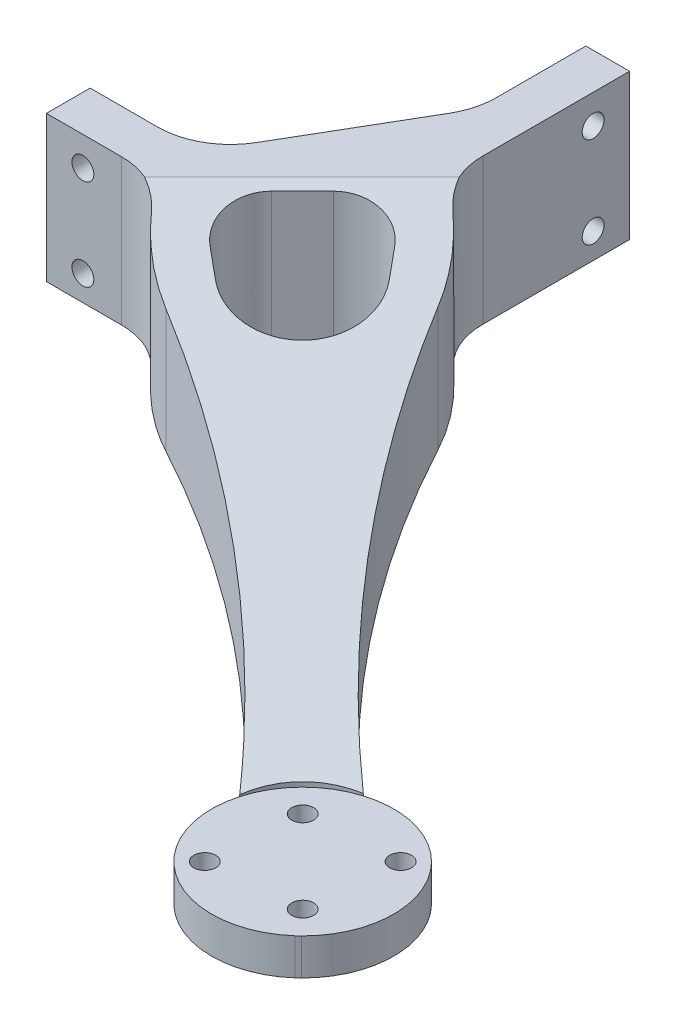
SolidWorks part; units mm, degrees
ref_plane "Front Plane" through (0, 0, 0) normal (0, 0, 1) x (1, 0, 0)
ref_plane "Top Plane" through (0, 0, 0) normal (0, 1, 0) x (1, 0, 0)
ref_plane "Right Plane" through (0, 0, 0) normal (1, 0, 0) x (0, 0, -1)
sketch "Sketch1" plane through (0, 0, 0) normal (0, 1, 0) x (1, 0, 0)
  line L0 (-32.8333, 3.1667) -> (-17.8333, 3.1667)
  line L1 (-17.8333, 3.1667) -> (7.1667, 18.1667)
  line L2 (7.1667, 18.1667) -> (7.1667, 33.1667)
  line L3 (7.1667, 33.1667) -> (12.1667, 33.1667)
  line L4 (12.1667, 33.1667) -> (12.1667, 18.1667)
  line L8 (-7.8333, -1.8333) -> (-32.8333, -1.8333)
  line L9 (-32.8333, -1.8333) -> (-32.8333, 3.1667)
  line L11 (12.1667, 18.1667) -> (17.5272, 18.1667)
  line L12 (-7.8333, -1.8333) -> (-7.8333, -7.1938)
  arc A0 (56.4946, -55.8323) -> (66.1657, -46.1613) centre (65.8063, -55.4729) ccw
  arc A1 (56.4946, -55.8323) -> (-7.8333, -7.1938) centre (-62.8059, -146.7575) ccw
  arc A2 (17.5272, 18.1667) -> (66.1657, -46.1613) centre (157.0908, 73.1392) ccw
  dimension "D1" = 15
  dimension "D2" = 5
  dimension "D3" = 15
  dimension "D4" = 5
  dimension "D5" = 25
  dimension "D6" = 25
  dimension "D7" = 15
  dimension "D8" = 15
  dimension "D11" = 155
  dimension "D14" = 155
extrude "Boss-Extrude3" add sketch "Sketch1" along normal blind 25
chamfer "Chamfer2" distance 6 angle 33 2 edges at (-7.8333, 12.5, 7.1938) (17.5272, 12.5, -18.1667) first distance on face at (-7.8333, 12.5, 4.5136) first distance on face at (39.6443, 12.5, 15.6623)
fillet "Fillet2" radius 30 2 edges at (19.7268, 12.5, -12.8805) (-2.8836, 12.5, 9.2464)
sketch "Sketch2" plane through (0, 0, 1.8333) normal (0, 0, 1) x (1, 0, 0)
  line L0 (-32.8333, 0) -> (-7.5027, 0) construction
  circle A0 centre (-27.8333, 20) radius 1.5
  circle A1 centre (-27.8333, 7.5) radius 1.5
  dimension "D1" = 20
  dimension "D3" = 12.5
  dimension "D2" = 35
extrude "Cut-Extrude1" cut sketch "Sketch2" against normal blind 25
sketch "Sketch3" plane through (12.1667, 0, 0) normal (1, 0, 0) x (0, 0, -1)
  line L0 (18.0687, 25) -> (33.1667, 25) construction
  circle A0 centre (28.1667, 20) radius 1.5
  circle A1 centre (28.1667, 7.5) radius 1.5
  dimension "D1" = 25
  dimension "D3" = 12.5
  dimension "D2" = 5
extrude "Cut-Extrude2" cut sketch "Sketch3" against normal blind 25
sketch "Sketch4" plane through (0, 25, 0) normal (0, 1, 0) x (1, 0, 0)
  line L0 (17.1652, 5.2091) -> (10.4484, 13.8698)
  line L1 (10.4484, 13.8698) -> (-3.4214, 0)
  line L2 (-3.4214, 0) -> (5.2393, -6.7168)
  arc A0 (56.4946, -55.8323) -> (4.4419, -12.6764) centre (-62.8059, -146.7575) ccw construction
  arc A1 (22.8804, 6.15) -> (66.1657, -46.1613) centre (157.0908, 73.1392) ccw construction
  arc A2 (22.8804, 6.15) -> (66.1657, -46.1613) centre (157.0908, 73.1392) ccw construction
  arc A4 (5.2393, -6.7168) -> (17.1652, 5.2091) centre (10.4484, 0) ccw
extrude "Cut-Extrude4" cut sketch "Sketch4" against normal blind 25
fillet "Fillet3" radius 6 2 edges at (10.4484, 12.5, -13.8698) (-3.4214, 12.5, 0)
sketch "Sketch7" plane through (0, 25, 0) normal (0, 1, 0) x (1, 0, 0)
  line L0 (8.9535, 27.4642) -> (42.7588, -6.3411)
  line L1 (42.7588, -6.3411) -> (46.7756, -2.3243)
  line L2 (46.7756, -2.3243) -> (12.9703, 31.481)
  line L3 (12.9703, 31.481) -> (8.9535, 27.4642)
extrude "Boss-Extrude4" add sketch "Sketch7" along normal blind 25
sketch "Sketch10" plane through (22.2256, 0, -22.2256) normal (0.7071, 0, -0.7071) x (-0.7071, 0, -0.7071)
  line L0 (-95.076, 0) -> (-95.076, 5)
  line L1 (-95.076, 25) -> (-95.076, 0) construction
  line L2 (-95.076, 5) -> (-72.576, 5)
  line L3 (-72.576, 5) -> (4.1734, 25)
  line L4 (4.1734, 25) -> (18.3848, 25)
  line L5 (18.3848, 25) -> (25.4558, 25)
  line L6 (18.3848, 25) -> (18.3848, 0) construction
  line L7 (18.3848, 5) -> (4.1734, 5)
  line L8 (4.1734, 25) -> (4.1734, 0) construction
  line L9 (4.1734, 5) -> (-65.076, 0)
  line L10 (-79.4271, 0) -> (-11.8302, 0) construction
  line L11 (-65.076, 0) -> (-95.076, 0)
  line L12 (25.4558, 25) -> (25.4558, 5)
  line L13 (-116.8035, -30.6808) -> (43.3804, -30.6808)
  line L14 (-116.8035, -30.6808) -> (-116.8035, 52.4335)
  line L15 (-116.8035, 52.4335) -> (43.3804, 52.4335)
  line L16 (43.3804, -30.6808) -> (43.3804, 52.4335)
  line L17 (25.4558, 25) -> (25.4558, 0) construction
  line L18 (25.4558, 5) -> (18.3848, 5)
  dimension "D1" = 22.5
  dimension "D2" = 30
  dimension "D3" = 5
  dimension "D4" = 20
extrude "Cut-Extrude6" cut sketch "Sketch10" against normal blind 100 and the other way blind 100
sketch "Sketch11" plane through (0, 5, 0) normal (0, 1, 0) x (1, 0, 0)
  circle A0 centre (63.6345, -53.1462) radius 12.5
  arc A1 (56.4946, -55.8323) -> (66.1657, -46.1613) centre (65.8063, -55.4729) ccw construction
  point P2 (72.3955, -62.0622)
  dimension "D1" = 12.5
extrude "Boss-Extrude5" add sketch "Sketch11" against normal up to surface (5 mm away) up to face at (59.0278, 0, 48.6945)
sketch "Sketch12" plane through (0, 5, 0) normal (0, 1, 0) x (1, 0, 0)
  circle A0 centre (63.6345, -53.1462) radius 12.5
extrude "Cut-Extrude7" cut sketch "Sketch12" along normal blind 100
fillet "Fillet5" radius 10 2 edges at (-17.8333, 15, -3.1667) (7.1667, 15, -18.1667)
sketch "Sketch13" plane through (0, 25, 0) normal (0, 1, 0) x (1, 0, 0)
  line L0 (-32.8333, 3.1667) -> (-7.8333, 3.1667)
  line L1 (-7.8333, 3.1667) -> (7.1667, 28.1667)
  line L3 (7.1667, 33.1667) -> (7.1667, 23.8286) construction
  line L4 (7.1667, 28.1667) -> (7.1667, 43.1667)
  line L5 (7.1667, 43.1667) -> (12.1667, 43.1667)
  line L6 (12.1667, 43.1667) -> (12.1667, 18.0687)
  line L7 (12.1667, 18.0687) -> (-7.7354, -1.8333)
  line L8 (-7.7354, -1.8333) -> (-32.8333, -1.8333)
  line L9 (-32.8333, -1.8333) -> (-32.8333, 3.1667)
  dimension "D1" = 15
  dimension "D2" = 25
  dimension "D3" = 5
  dimension "D4" = 15
extrude "Boss-Extrude9" add sketch "Sketch13" against normal up to surface (20 mm away) up to face at (-6.7259, 5, -12.9753)
sketch "Sketch14" plane through (0, 25, 0) normal (0, 1, 0) x (1, 0, 0)
  line L0 (-23.4908, 3.1667) -> (-7.8333, 3.1667)
  line L1 (-20.6032, 3.1667) -> (-32.8333, 3.1667) construction
  line L2 (-7.8333, 3.1667) -> (-1.1639, 14.2824)
  line L3 (7.1667, 28.1667) -> (-2.2083, 12.5417) construction
  line L4 (-1.1639, 14.2824) -> (-23.4908, 3.1667)
  dimension "D1" = 15
  dimension "D2" = 25
extrude "Cut-Extrude9" cut sketch "Sketch14" against normal blind 100
sketch "Sketch15" plane through (0, 25, 0) normal (0, 1, 0) x (1, 0, 0)
  line L0 (-32.8333, -1.8333) -> (-32.8333, 3.1667)
  line L1 (-32.8333, 3.1667) -> (-22.8333, 3.1667)
  line L2 (-7.8333, 3.1667) -> (-32.8333, 3.1667) construction
  line L3 (-22.8333, 3.1667) -> (-22.8333, -1.8333)
  line L4 (-32.8333, -1.8333) -> (-7.7354, -1.8333) construction
  line L5 (-22.8333, -1.8333) -> (-32.8333, -1.8333)
  dimension "D1" = 15
extrude "Cut-Extrude10" cut sketch "Sketch15" against normal blind 100
sketch "Sketch16" plane through (7.1667, 0, 0) normal (-1, 0, 0) x (0, 0, 1)
  line L0 (-43.1667, 5) -> (-43.1667, 25) construction
  line L1 (-43.1667, 25) -> (-28.1667, 25) construction
  circle A0 centre (-38.1667, 21) radius 1.5
  circle A1 centre (-38.1667, 8.5) radius 1.5
  dimension "D1" = 5
  dimension "D3" = 12.5
  dimension "D2" = 4
extrude "Cut-Extrude11" cut sketch "Sketch16" against normal blind 10
sketch "Sketch17" plane through (0, 0, -3.1667) normal (0, 0, -1) x (-1, 0, 0)
  line L0 (7.8333, 25) -> (22.8333, 25) construction
  line L1 (22.8333, 5) -> (22.8333, 25) construction
  circle A0 centre (17.8333, 21) radius 1.5
  circle A1 centre (17.8333, 8.5) radius 1.5
  dimension "D1" = 4
  dimension "D3" = 12.5
  dimension "D2" = 5
extrude "Cut-Extrude12" cut sketch "Sketch17" against normal blind 10
fillet "Fillet7" radius 10 2 edges at (-7.5027, 14.9726, 1.8333) (12.1667, 15, -18.0687)
sketch "Sketch18" plane through (0, 5, 0) normal (0, 1, 0) x (1, 0, 0)
  circle A0 centre (56.917, -59.8637) radius 1.5
  circle A2 centre (70.352, -46.4287) radius 1.5
  circle A3 centre (57.9776, -47.4894) radius 1.5
  circle A4 centre (69.2914, -58.8031) radius 1.5
  dimension "D1" = 16
  dimension "D3" = 19
extrude "Cut-Extrude14" cut sketch "Sketch18" against normal blind 10
sketch "Sketch20" plane through (0, 0, 0) normal (0, -1, 0) x (1, 0, 0)
  line L0 (62.2203, 49.6107) -> (60.2334, 51.8664)
  line L2 (67.17, 54.5604) -> (62.2203, 49.6107)
  line L5 (60.2334, 51.8664) -> (65.1831, 56.8162)
  line L7 (60.2334, 51.8664) -> (65.1831, 56.8162)
  line L8 (65.1831, 56.8162) -> (67.17, 54.5604)
  line L9 (67.17, 54.5604) -> (62.2203, 49.6107)
  dimension "D2" = 7
extrude "Boss-Extrude10" add sketch "Sketch20" along normal blind 7 contours L8 L5 L0 L2 region at (63.7017, 0, 53.2134)
sketch "Sketch21" plane through (6.3048, 0, -6.3048) normal (0.7071, 0, -0.7071) x (-0.7071, 0, -0.7071)
  line L0 (-86.0764, -7) -> (-86.0764, 0) construction
  line L1 (-86.0764, -7) -> (-79.0764, -7) construction
  circle A0 centre (-82.5764, -4.5) radius 1.5
  point P4 (-82.5764, -7)
  dimension "D1" = 3.5
  dimension "D2" = 2.5
extrude "Cut-Extrude15" cut sketch "Sketch21" against normal blind 7
fillet "Fillet8" radius 3.5 2 edges at (66.1766, -7, 55.6883) (61.2268, -7, 50.7386)
sketch "Sketch24" plane through (0.2386, 4.6743, 0.2386) normal (-0.0509, -0.9974, -0.0509) x (-0.9987, 0.0509, 0.0026)
  line L0 (-41.0214, -32.9045) -> (-43.1427, -30.7832)
  line L1 (-43.1427, -30.7832) -> (-41.0214, -28.6619)
  line L2 (-41.0214, -28.6619) -> (-38.9001, -30.7832)
  line L3 (-38.9001, -30.7832) -> (-41.0214, -32.9045)
  line L4 (-41.0214, -28.6619) -> (-52.0696, -39.7389)
  line L5 (-54.9743, -36.8417) -> (-47.0454, -44.75) construction
  line L6 (-52.0696, -39.7389) -> (-54.9743, -36.8417)
  line L7 (-41.0214, -32.9045) -> (-49.9483, -41.8547)
  line L8 (-49.9483, -41.8547) -> (-47.0454, -44.75)
  dimension "D1" = 3
  dimension "D2" = 3
  dimension "D3" = 4.1
extrude "Boss-Extrude13" add sketch "Sketch24" along normal blind 5 contours L2 L4 L0 L3 region at (41.2059, 1.0185, 30.8758)
sketch "Sketch25" plane through (6.225, 0, -6.225) normal (0.7071, 0, -0.7071) x (-0.7071, 0, -0.7071)
  line L0 (-49.1116, -3.8603) -> (-49.4717, 1.1267) construction
  line L1 (-49.1116, -3.8603) -> (-52.1038, -4.0764) construction
  line L2 (-49.9193, -1.4749) -> (-49.338, -0.7249)
  line L3 (-49.338, -0.7249) -> (-49.4102, 0.2751)
  line L4 (-49.4102, 0.2751) -> (-50.2426, -0.7988)
  arc A0 (-50.2426, -0.7988) -> (-49.9193, -1.4749) centre (-50.7878, -1.4749) ccw
  dimension "D1" = 1.5
  dimension "D2" = 2.5
  dimension "D3" = 1
  dimension "D4" = 0.75
extrude "Cut-Extrude16" cut sketch "Sketch25" against normal blind 5
sketch "Sketch26" plane through (6.225, 0, -6.225) normal (0.7071, 0, -0.7071) x (-0.7071, 0, -0.7071)
  line L1 (-53.1709, -2.6052) -> (-47.8537, -2.8247)
  line L2 (-47.8537, -2.8247) -> (-48.0538, -4.7789)
  line L3 (-48.0538, -4.7789) -> (-52.9981, -4.9223)
  line L4 (-52.9981, -4.9223) -> (-53.1709, -2.6052)
extrude "Cut-Extrude18" cut sketch "Sketch26" against normal blind 5
fillet "Fillet10" radius 1 2 edges at (42.0832, -2.6449, 31.7517) (39.9486, -2.7694, 29.6199)
sketch "Sketch27" plane through (7.1667, 0, 0) normal (-1, 0, 0) x (0, 0, 1)
  line L1 (-43.1667, 5) -> (-28.1667, 5)
  line L2 (-43.1667, 5) -> (-43.1667, 25)
  line L3 (-43.1667, 25) -> (-28.1667, 25)
  line L4 (-28.1667, 5) -> (-28.1667, 25)
  circle A0 centre (-38.1667, 21) radius 1.5
  circle A1 centre (-38.1667, 8.5) radius 1.5
extrude "Boss-Extrude14" add sketch "Sketch27" along normal blind 1
sketch "Sketch28" plane through (0, 0, -3.1667) normal (0, 0, -1) x (-1, 0, 0)
  line L1 (7.8333, 5) -> (22.8333, 5)
  line L2 (7.8333, 5) -> (7.8333, 25)
  line L3 (7.8333, 25) -> (22.8333, 25)
  line L4 (22.8333, 5) -> (22.8333, 25)
  circle A0 centre (17.8333, 21) radius 1.5
  circle A1 centre (17.8333, 8.5) radius 1.5
extrude "Boss-Extrude15" add sketch "Sketch28" along normal blind 1
sketch "Sketch29" plane through (0, 25, 0) normal (0, 1, 0) x (1, 0, 0)
  line L0 (7.1667, 28.1667) -> (-7.8333, 3.1667)
  line L1 (-7.8333, 3.1667) -> (-7.8333, 4.1667)
  line L2 (-7.8333, 4.1667) -> (-7.8333, 3.1667) construction
  line L3 (-22.8333, 4.1667) -> (-7.8333, 4.1667) construction
  line L4 (7.1667, 28.1667) -> (6.1667, 28.1667)
  line L6 (6.1667, 28.1667) -> (-7.8333, 4.1667)
extrude "Boss-Extrude16" add sketch "Sketch29" against normal up to surface (20 mm away) up to face at (-2.1432, 5, -15.8322)
fillet "Fillet11" radius 10 2 edges at (-7.8333, 15, -4.1667) (6.1667, 15, -28.1667)
